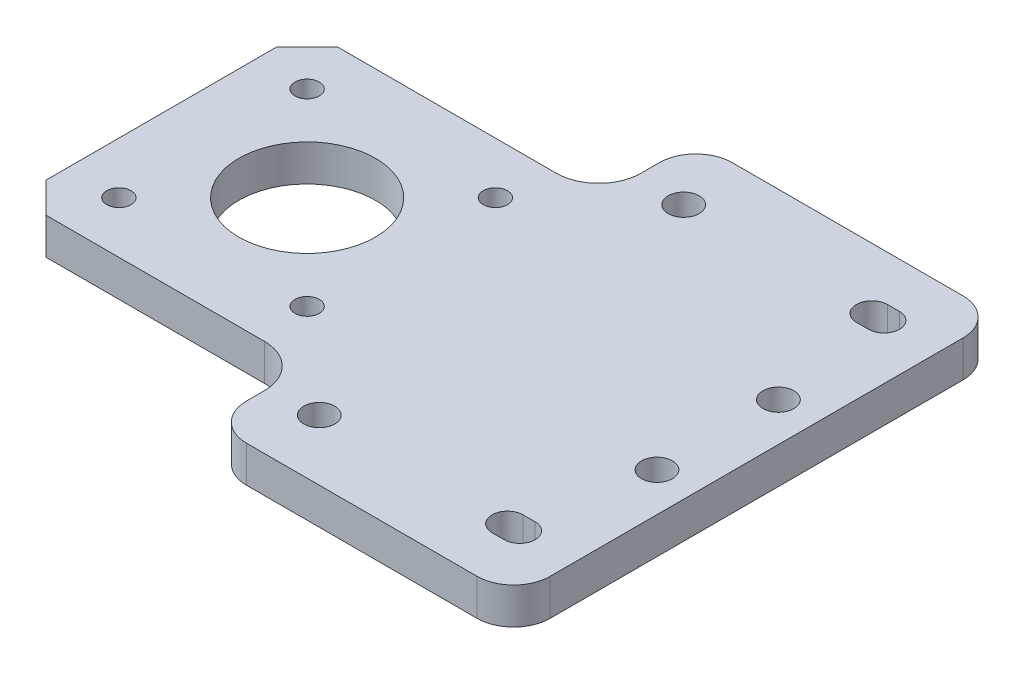
SolidWorks part; units mm, degrees
material "Клен"
ref_plane "Спереди" through (0, 0, 0) normal (0, 0, 1) x (1, 0, 0)
ref_plane "Сверху" through (0, 0, 0) normal (0, 1, 0) x (1, 0, 0)
ref_plane "Справа" through (0, 0, 0) normal (1, 0, 0) x (0, 0, -1)
sketch "Эскиз1" plane through (0, 0, 0) normal (0, 1, 0) x (1, 0, 0)
  line L0 (-56.8562, 0) -> (56.8562, 0) construction
  line L9 (-32, -24) -> (-68, -24)
  line L10 (-19, -40) -> (19, -40)
  line L11 (-25, -34) -> (-25, -31)
  line L12 (-19, 40) -> (19, 40)
  line L13 (25, -34) -> (25, 34)
  line L14 (-25, -40) -> (25, 40) construction
  line L15 (-25, 40) -> (25, -40) construction
  line L20 (-73, -19) -> (-73, 19)
  line L21 (-32, 24) -> (-68, 24)
  line L22 (-25, 31) -> (-25, 34)
  line L23 (-68, -24) -> (-73, -19)
  line L24 (-68, 24) -> (-73, 19)
  line L25 (-73, -24) -> (-25, 24) construction
  line L26 (-25, -24) -> (-72.5248, 23.5248) construction
  line L27 (-49, -29.3961) -> (-49, 34.1878) construction
  line L28 (12.105, -10) -> (440.105, -10) construction
  line L29 (12.105, -10.6243) -> (12.105, -12.7157) construction
  arc A4 (19, 40) -> (25, 34) centre (19, 34) cw
  arc A5 (19, -40) -> (25, -34) centre (19, -34) ccw
  arc A6 (-19, -40) -> (-25, -34) centre (-19, -34) cw
  arc A7 (-25, 34) -> (-19, 40) centre (-19, 34) cw
  circle A8 centre (-49, 0) radius 11.25
  circle A9 centre (-64.5, 15.5) radius 2
  circle A10 centre (-64.5, -15.5) radius 2
  circle A11 centre (-33.5, 15.5) radius 2
  circle A12 centre (-33.5, -15.5) radius 2
  arc A13 (-25, -31) -> (-32, -24) centre (-32, -31) ccw
  arc A14 (-32, 24) -> (-25, 31) centre (-32, 31) ccw
  circle A15 centre (18.605, -10) radius 2.55
  circle A16 centre (18.605, 10) radius 2.55
  point P0 (0, 0)
  point P22 (-73, -24)
  point P24 (-73, 24)
  point P25 (-75, 0)
  point P32 (-49, 0)
  point P34 (-49.8171, 0.0009)
  point P35 (-49, 0)
  point P36 (-24.7404, 0.0009)
  point P37 (-49, 0)
  point P39 (-49, 0)
  point P56 (-25, 32.5)
  dimension "D1" = 6
  dimension "D6" = 22.5
  dimension "D7" = 4
  dimension "D13" = 7
  dimension "D14" = 7
  dimension "D15" = 5.1
  dimension "D2" = 80
  dimension "D3" = 50
  dimension "D4" = 48
  dimension "D10" = 15.5
  dimension "D11" = 15.5
  dimension "D12" = 15.5
  dimension "D5" = 48
  dimension "D17" = 6.5
extrude "Бобышка-Вытянуть1" add sketch "Эскиз1" along normal blind 6
sketch "Эскиз2" plane through (0, 0, 0) normal (0, -1, 0) x (1, 0, 0)
  line L0 (0, -37.0349) -> (0, 29.2907) construction
  line L1 (16, -30) -> (14, -30) construction
  line L2 (16, -32.55) -> (14, -32.55)
  line L3 (16, -27.45) -> (14, -27.45)
  line L6 (-46.1924, 0) -> (55.6646, 0) construction
  line L7 (16, 30) -> (14, 30) construction
  line L8 (16, 32.55) -> (14, 32.55)
  line L9 (16, 27.45) -> (14, 27.45)
  line L10 (-25, 31) -> (-25, 34) construction
  line L11 (19, -40) -> (-19, -40) construction
  circle A0 centre (-17, -30) radius 2.55
  arc A1 (16, -32.55) -> (16, -27.45) centre (16, -30) ccw
  arc A2 (14, -27.45) -> (14, -32.55) centre (14, -30) ccw
  arc A3 (16, 32.55) -> (16, 27.45) centre (16, 30) cw
  arc A4 (14, 27.45) -> (14, 32.55) centre (14, 30) cw
  circle A5 centre (-17, 30) radius 2.55
  point P7 (15, -30)
  point P12 (15, -32.55)
  point P21 (15, 30)
  dimension "D1" = 5.1
  dimension "D2" = 5.1
  dimension "D4" = 33
  dimension "D5" = 8
  dimension "D6" = 10
extrude "Вырез-Вытянуть1" cut sketch "Эскиз2" against normal through all
equation "\"D2@Эскиз2\"=\"D1@Эскиз2\""
equation "\"D5@Эскиз1\"=\"D4@Эскиз1\""
